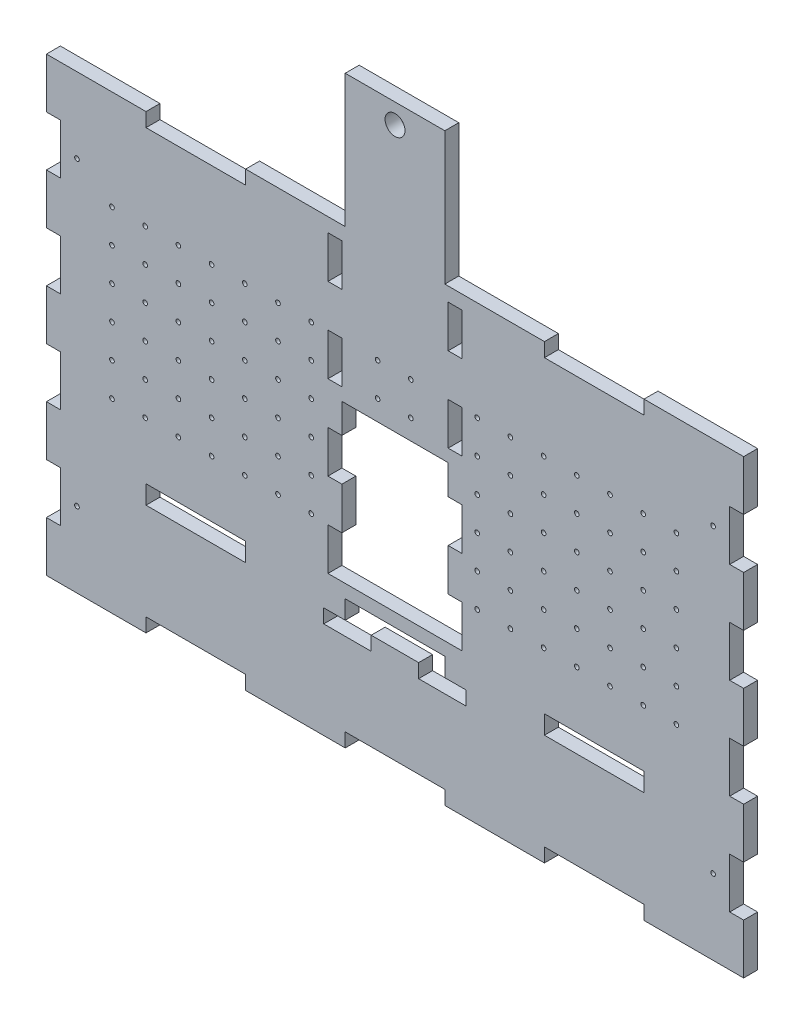
SolidWorks part; units mm, degrees
ref_plane "Front Plane" through (0, 0, 0) normal (0, 0, 1) x (1, 0, 0)
ref_plane "Top Plane" through (0, 0, 0) normal (0, 1, 0) x (1, 0, 0)
ref_plane "Right Plane" through (0, 0, 0) normal (1, 0, 0) x (0, 0, -1)
sketch "Sketch1" plane through (0, 0, 0) normal (0, 0, 1) x (1, 0, 0)
  line L1 (-127.8759, 88.4641) -> (138.8241, 88.4641)
  line L2 (-127.8759, 88.4641) -> (-127.8759, -84.2559)
  line L3 (-127.8759, -84.2559) -> (138.8241, -84.2559)
  line L4 (138.8241, 88.4641) -> (138.8241, -84.2559)
  dimension "D1" = 266.7
  dimension "D2" = 172.72
extrude "Boss-Extrude1" add sketch "Sketch1" along normal blind 5.334
sketch "Sketch2" plane through (0, 0, 5.334) normal (0, 0, 1) x (1, 0, 0)
  line L0 (-127.8759, -84.2559) -> (138.8241, -84.2559) construction
  line L1 (-89.7759, -84.2559) -> (-51.6759, -84.2559)
  line L2 (-89.7759, -84.2559) -> (-89.7759, -78.9219)
  line L3 (-89.7759, -78.9219) -> (-51.6759, -78.9219)
  line L4 (-51.6759, -84.2559) -> (-51.6759, -78.9219)
  line L5 (-89.7759, -78.9219) -> (-127.8759, -78.9219) construction
  line L6 (-13.5759, -84.2559) -> (24.5241, -84.2559)
  line L7 (-13.5759, -84.2559) -> (-13.5759, -78.9219)
  line L8 (-13.5759, -78.9219) -> (24.5241, -78.9219)
  line L9 (24.5241, -84.2559) -> (24.5241, -78.9219)
  line L10 (62.6241, -84.2559) -> (100.7241, -84.2559)
  line L11 (62.6241, -84.2559) -> (62.6241, -78.9219)
  line L12 (62.6241, -78.9219) -> (100.7241, -78.9219)
  line L13 (100.7241, -84.2559) -> (100.7241, -78.9219)
  line L14 (-127.8759, 88.4641) -> (-127.8759, -84.2559) construction
  line L15 (-51.6759, -78.9219) -> (-13.5759, -78.9219) construction
  line L16 (24.5241, -78.9219) -> (62.6241, -78.9219) construction
  line L17 (62.6241, -78.9219) -> (62.364, -79.7896) construction
  line L18 (100.7241, -78.9219) -> (138.8241, -78.9219) construction
  line L19 (138.8241, -84.2559) -> (138.8241, 88.4641) construction
  line L20 (-127.8759, 2.1041) -> (138.8241, 2.1041) construction
  line L21 (100.7241, 88.4641) -> (100.7241, 83.1301)
  line L22 (62.6241, 83.1301) -> (100.7241, 83.1301)
  line L23 (62.6241, 88.4641) -> (62.6241, 83.1301)
  line L24 (24.5241, 88.4641) -> (24.5241, 83.1301)
  line L25 (-13.5759, 83.1301) -> (24.5241, 83.1301)
  line L26 (-13.5759, 88.4641) -> (-13.5759, 83.1301)
  line L27 (-51.6759, 88.4641) -> (-51.6759, 83.1301)
  line L28 (-89.7759, 83.1301) -> (-51.6759, 83.1301)
  line L29 (-89.7759, 88.4641) -> (-89.7759, 83.1301)
  line L30 (62.6241, 88.4641) -> (100.7241, 88.4641)
  line L31 (-13.5759, 88.4641) -> (24.5241, 88.4641)
  line L32 (-89.7759, 88.4641) -> (-51.6759, 88.4641)
  dimension "D1" = 5.334
extrude "Cut-Extrude1" cut sketch "Sketch2" against normal through all
sketch "Sketch5" plane through (0, 0, 5.334) normal (0, 0, 1) x (1, 0, 0)
  line L0 (-51.6759, -34.8224) -> (-13.5759, -34.8224) construction
  line L1 (-89.7759, -34.8224) -> (-51.6759, -34.8224)
  line L2 (-89.7759, -34.8224) -> (-89.7759, -41.9344)
  line L3 (-89.7759, -41.9344) -> (-51.6759, -41.9344)
  line L4 (-51.6759, -34.8224) -> (-51.6759, -41.9344)
  line L5 (-13.5759, -34.8224) -> (24.5241, -34.8224)
  line L6 (-13.5759, -34.8224) -> (-13.5759, -41.9344)
  line L7 (-13.5759, -41.9344) -> (24.5241, -41.9344)
  line L8 (24.5241, -34.8224) -> (24.5241, -41.9344)
  line L9 (62.6241, -34.8224) -> (100.7241, -34.8224)
  line L10 (62.6241, -34.8224) -> (62.6241, -41.9344)
  line L11 (62.6241, -41.9344) -> (100.7241, -41.9344)
  line L12 (100.7241, -34.8224) -> (100.7241, -41.9344)
  line L13 (-51.6759, -41.9344) -> (-13.5759, -41.9344) construction
  line L14 (24.5241, -34.8224) -> (62.6241, -34.8224) construction
  line L15 (24.5241, -41.9344) -> (62.6241, -41.9344) construction
  line L16 (-89.7759, -34.8224) -> (-127.8759, -34.8224) construction
  line L17 (-127.8759, 88.4641) -> (-127.8759, -84.2559) construction
  line L18 (-89.7759, -41.9344) -> (-127.8759, -41.9344) construction
  line L19 (100.7241, -34.8224) -> (138.8241, -34.8224) construction
  line L20 (138.8241, -84.2559) -> (138.8241, 88.4641) construction
  line L21 (100.7241, -41.9344) -> (138.8241, -41.9344) construction
  dimension "D1" = 7.112
extrude "Cut-Extrude3" cut sketch "Sketch5" against normal through all
sketch "Sketch8" plane through (0, 0, 5.334) normal (0, 0, 1) x (1, 0, 0)
  line L0 (-13.5759, -41.9344) -> (24.5241, -41.9344) construction
  line L1 (-21.7977, -47.2684) -> (-3.6478, -47.2684)
  line L2 (-21.7977, -47.2684) -> (-21.7977, -41.9344)
  line L3 (-21.7977, -41.9344) -> (-3.6478, -41.9344)
  line L4 (-3.6478, -47.2684) -> (-3.6478, -41.9344)
  line L5 (-3.6478, -47.2684) -> (14.5022, -47.2684) construction
  line L6 (14.5022, -41.9344) -> (32.6521, -41.9344)
  line L7 (14.5022, -41.9344) -> (14.5022, -47.2684)
  line L8 (14.5022, -47.2684) -> (32.6521, -47.2684)
  line L9 (32.6521, -41.9344) -> (32.6521, -47.2684)
  line L10 (14.5022, -47.2684) -> (14.3218, -49.4005) construction
  line L11 (14.5022, -41.9344) -> (-3.6478, -41.9344) construction
  line L12 (62.6241, -34.8224) -> (62.6241, -41.9344) construction
  line L13 (-51.6759, -41.9344) -> (-51.6759, -34.8224) construction
  dimension "D1" = 5.334
  dimension "D2" = 29.972
  dimension "D3" = 29.8782
extrude "Cut-Extrude6" cut sketch "Sketch8" against normal through all
sketch "Sketch9" plane through (0, 0, 5.334) normal (0, 0, 1) x (1, 0, 0)
  line L0 (-127.8759, 88.4641) -> (-127.8759, -84.2559) construction
  line L1 (-127.8759, -65.0647) -> (-122.5419, -65.0647)
  line L2 (-127.8759, -65.0647) -> (-127.8759, -45.8736)
  line L3 (-127.8759, -45.8736) -> (-122.5419, -45.8736)
  line L4 (-122.5419, -65.0647) -> (-122.5419, -45.8736)
  line L5 (-122.5419, 69.273) -> (-122.5419, 88.4641) construction
  line L6 (-127.8759, -26.6825) -> (-122.5419, -26.6825)
  line L7 (-127.8759, -26.6825) -> (-127.8759, -7.4914)
  line L8 (-127.8759, -7.4914) -> (-122.5419, -7.4914)
  line L9 (-122.5419, -26.6825) -> (-122.5419, -7.4914)
  line L10 (-127.8759, 11.6997) -> (-122.5419, 11.6997)
  line L11 (-127.8759, 11.6997) -> (-127.8759, 30.8908)
  line L12 (-127.8759, 30.8908) -> (-122.5419, 30.8908)
  line L13 (-122.5419, 11.6997) -> (-122.5419, 30.8908)
  line L14 (-127.8759, 50.0819) -> (-122.5419, 50.0819)
  line L15 (-127.8759, 50.0819) -> (-127.8759, 69.273)
  line L16 (-127.8759, 69.273) -> (-122.5419, 69.273)
  line L17 (-122.5419, 50.0819) -> (-122.5419, 69.273)
  line L18 (-89.7759, 88.4641) -> (-127.8759, 88.4641) construction
  line L19 (-122.5419, 50.0819) -> (-122.5419, 30.8908) construction
  line L20 (-122.5419, 11.6997) -> (-122.5419, -7.4914) construction
  line L21 (-122.5419, -26.6825) -> (-122.5419, -45.8736) construction
  line L22 (-122.5419, -65.0647) -> (-122.5419, -84.2559) construction
  line L23 (-127.8759, -84.2559) -> (-89.7759, -84.2559) construction
  line L24 (5.4741, 83.1301) -> (5.4741, -78.9219) construction
  line L25 (-13.5759, 83.1301) -> (24.5241, 83.1301) construction
  line L26 (24.5241, -78.9219) -> (-13.5759, -78.9219) construction
  line L27 (133.4901, -65.0647) -> (133.4901, -84.2559) construction
  line L28 (133.4901, -26.6825) -> (133.4901, -45.8736) construction
  line L29 (133.4901, 11.6997) -> (133.4901, -7.4914) construction
  line L30 (133.4901, 50.0819) -> (133.4901, 30.8908) construction
  line L31 (133.4901, 69.273) -> (133.4901, 88.4641) construction
  line L32 (133.4901, 50.0819) -> (133.4901, 69.273)
  line L33 (138.8241, 69.273) -> (133.4901, 69.273)
  line L34 (138.8241, 50.0819) -> (138.8241, 69.273)
  line L35 (138.8241, 50.0819) -> (133.4901, 50.0819)
  line L36 (133.4901, 11.6997) -> (133.4901, 30.8908)
  line L37 (138.8241, 30.8908) -> (133.4901, 30.8908)
  line L38 (138.8241, 11.6997) -> (138.8241, 30.8908)
  line L39 (138.8241, 11.6997) -> (133.4901, 11.6997)
  line L40 (133.4901, -26.6825) -> (133.4901, -7.4914)
  line L41 (138.8241, -7.4914) -> (133.4901, -7.4914)
  line L42 (138.8241, -26.6825) -> (138.8241, -7.4914)
  line L43 (138.8241, -26.6825) -> (133.4901, -26.6825)
  line L44 (133.4901, -65.0647) -> (133.4901, -45.8736)
  line L45 (138.8241, -45.8736) -> (133.4901, -45.8736)
  line L46 (138.8241, -65.0647) -> (138.8241, -45.8736)
  line L47 (138.8241, -65.0647) -> (133.4901, -65.0647)
  dimension "D1" = 5.334
extrude "Cut-Extrude7" cut sketch "Sketch9" against normal through all
sketch "Sketch10" plane through (0, 88.4641, 0) normal (0, 1, 0) x (1, 0, 0)
  line L1 (24.5241, -5.334) -> (62.6241, -5.334)
  line L2 (24.5241, -5.334) -> (24.5241, 0)
  line L3 (24.5241, 0) -> (62.6241, 0)
  line L4 (62.6241, -5.334) -> (62.6241, 0)
extrude "Boss-Extrude2" add sketch "Sketch10" along normal blind 50.8
sketch "Sketch11" plane through (0, 0, 0) normal (0, 0, -1) x (-1, 0, 0)
  line L0 (-24.5241, 83.1301) -> (-24.5241, 139.2641) construction
  line L1 (-24.5241, 88.4641) -> (-31.1281, 88.4641)
  line L2 (-24.5241, 88.4641) -> (-24.5241, 129.1041)
  line L3 (-24.5241, 129.1041) -> (-31.1281, 129.1041)
  line L4 (-31.1281, 88.4641) -> (-31.1281, 129.1041)
  line L5 (13.5759, 88.4641) -> (51.6759, 88.4641) construction
  dimension "D1" = 6.604
  dimension "D2" = 40.64
  dimension "D3" = 0
extrude "Cut-Extrude8" cut sketch "Sketch11" against normal through all
sketch "Sketch12" plane through (0, 0, 5.334) normal (0, 0, 1) x (1, 0, 0)
  line L0 (62.6241, 139.2641) -> (62.6241, 83.1301) construction
  circle A0 centre (43.5741, 130.4765) radius 3.81
  dimension "D1" = 19.05
extrude "Cut-Extrude9" cut sketch "Sketch12" against normal through all
sketch "Sketch14" plane through (0, 0, 5.334) normal (0, 0, 1) x (1, 0, 0)
  line L0 (-89.7759, 88.4641) -> (-127.8759, 88.4641) construction
  circle A0 centre (-102.7976, 50.3641) radius 0.889
  circle A1 centre (-90.0976, 50.3641) radius 0.889
  circle A2 centre (-77.3976, 50.3641) radius 0.889
  circle A3 centre (-64.6976, 50.3641) radius 0.889
  circle A4 centre (-51.9976, 50.3641) radius 0.889
  circle A5 centre (-39.2976, 50.3641) radius 0.889
  circle A6 centre (-26.5976, 50.3641) radius 0.889
  circle A8 centre (-1.1976, 50.3641) radius 0.889
  circle A9 centre (11.5024, 50.3641) radius 0.889
  circle A11 centre (36.9024, 50.3641) radius 0.889
  circle A12 centre (49.6024, 50.3641) radius 0.889
  circle A13 centre (62.3024, 50.3641) radius 0.889
  circle A14 centre (75.0024, 50.3641) radius 0.889
  circle A15 centre (87.7024, 50.3641) radius 0.889
  circle A16 centre (100.4024, 50.3641) radius 0.889
  circle A17 centre (113.1024, 50.3641) radius 0.889
  circle A18 centre (-102.7976, 37.6641) radius 0.889
  circle A19 centre (-90.0976, 37.6641) radius 0.889
  circle A20 centre (-77.3976, 37.6641) radius 0.889
  circle A21 centre (-64.6976, 37.6641) radius 0.889
  circle A22 centre (-51.9976, 37.6641) radius 0.889
  circle A23 centre (-39.2976, 37.6641) radius 0.889
  circle A24 centre (-26.5976, 37.6641) radius 0.889
  circle A26 centre (-1.1976, 37.6641) radius 0.889
  circle A27 centre (11.5024, 37.6641) radius 0.889
  circle A29 centre (36.9024, 37.6641) radius 0.889
  circle A30 centre (49.6024, 37.6641) radius 0.889
  circle A31 centre (62.3024, 37.6641) radius 0.889
  circle A32 centre (75.0024, 37.6641) radius 0.889
  circle A33 centre (87.7024, 37.6641) radius 0.889
  circle A34 centre (100.4024, 37.6641) radius 0.889
  circle A35 centre (113.1024, 37.6641) radius 0.889
  circle A36 centre (-102.7976, 24.9641) radius 0.889
  circle A37 centre (-90.0976, 24.9641) radius 0.889
  circle A38 centre (-77.3976, 24.9641) radius 0.889
  circle A39 centre (-64.6976, 24.9641) radius 0.889
  circle A40 centre (-51.9976, 24.9641) radius 0.889
  circle A41 centre (-39.2976, 24.9641) radius 0.889
  circle A42 centre (-26.5976, 24.9641) radius 0.889
  circle A44 centre (-1.1976, 24.9641) radius 0.889
  circle A45 centre (11.5024, 24.9641) radius 0.889
  circle A47 centre (36.9024, 24.9641) radius 0.889
  circle A48 centre (49.6024, 24.9641) radius 0.889
  circle A49 centre (62.3024, 24.9641) radius 0.889
  circle A50 centre (75.0024, 24.9641) radius 0.889
  circle A51 centre (87.7024, 24.9641) radius 0.889
  circle A52 centre (100.4024, 24.9641) radius 0.889
  circle A53 centre (113.1024, 24.9641) radius 0.889
  circle A54 centre (-102.7976, 12.2641) radius 0.889
  circle A55 centre (-90.0976, 12.2641) radius 0.889
  circle A56 centre (-77.3976, 12.2641) radius 0.889
  circle A57 centre (-64.6976, 12.2641) radius 0.889
  circle A58 centre (-51.9976, 12.2641) radius 0.889
  circle A59 centre (-39.2976, 12.2641) radius 0.889
  circle A60 centre (-26.5976, 12.2641) radius 0.889
  circle A65 centre (36.9024, 12.2641) radius 0.889
  circle A66 centre (49.6024, 12.2641) radius 0.889
  circle A67 centre (62.3024, 12.2641) radius 0.889
  circle A68 centre (75.0024, 12.2641) radius 0.889
  circle A69 centre (87.7024, 12.2641) radius 0.889
  circle A70 centre (100.4024, 12.2641) radius 0.889
  circle A71 centre (113.1024, 12.2641) radius 0.889
  circle A72 centre (-102.7976, -0.4359) radius 0.889
  circle A73 centre (-90.0976, -0.4359) radius 0.889
  circle A74 centre (-77.3976, -0.4359) radius 0.889
  circle A75 centre (-64.6976, -0.4359) radius 0.889
  circle A76 centre (-51.9976, -0.4359) radius 0.889
  circle A77 centre (-39.2976, -0.4359) radius 0.889
  circle A78 centre (-26.5976, -0.4359) radius 0.889
  circle A79 centre (-13.8976, -0.4359) radius 0.889
  circle A80 centre (-1.1976, -0.4359) radius 0.889
  circle A81 centre (11.5024, -0.4359) radius 0.889
  circle A82 centre (24.2024, -0.4359) radius 0.889
  circle A83 centre (36.9024, -0.4359) radius 0.889
  circle A84 centre (49.6024, -0.4359) radius 0.889
  circle A85 centre (62.3024, -0.4359) radius 0.889
  circle A86 centre (75.0024, -0.4359) radius 0.889
  circle A87 centre (87.7024, -0.4359) radius 0.889
  circle A88 centre (100.4024, -0.4359) radius 0.889
  circle A89 centre (113.1024, -0.4359) radius 0.889
  circle A90 centre (-102.7976, -13.1359) radius 0.889
  circle A91 centre (-90.0976, -13.1359) radius 0.889
  circle A92 centre (-77.3976, -13.1359) radius 0.889
  circle A93 centre (-64.6976, -13.1359) radius 0.889
  circle A94 centre (-51.9976, -13.1359) radius 0.889
  circle A95 centre (-39.2976, -13.1359) radius 0.889
  circle A96 centre (-26.5976, -13.1359) radius 0.889
  circle A97 centre (-13.8976, -13.1359) radius 0.889
  circle A98 centre (-1.1976, -13.1359) radius 0.889
  circle A99 centre (11.5024, -13.1359) radius 0.889
  circle A100 centre (24.2024, -13.1359) radius 0.889
  circle A101 centre (36.9024, -13.1359) radius 0.889
  circle A102 centre (49.6024, -13.1359) radius 0.889
  circle A103 centre (62.3024, -13.1359) radius 0.889
  circle A104 centre (75.0024, -13.1359) radius 0.889
  circle A105 centre (87.7024, -13.1359) radius 0.889
  circle A106 centre (100.4024, -13.1359) radius 0.889
  circle A107 centre (113.1024, -13.1359) radius 0.889
  circle A108 centre (-1.1976, 12.2641) radius 0.889 [skipped]
  circle A110 centre (11.5024, 12.2641) radius 0.889 [skipped]
  circle A116 centre (24.2024, 50.3641) radius 0.889 [skipped]
  circle A117 centre (-13.8976, 50.3641) radius 0.889 [skipped]
  dimension "D1" = 18
  dimension "D2" = 38.1
  dimension "D4" = 1.778
  dimension "D3" = 6
extrude "Cut-Extrude11" cut sketch "Sketch14" against normal through all
sketch "Sketch15" plane through (0, 0, 5.334) normal (0, 0, 1) x (1, 0, 0)
  line L1 (31.1281, 129.1041) -> (24.5241, 129.1041)
  line L2 (31.1281, 129.1041) -> (31.1281, 139.2641)
  line L3 (31.1281, 139.2641) -> (24.5241, 139.2641)
  line L4 (24.5241, 129.1041) -> (24.5241, 139.2641)
extrude "Cut-Extrude12" cut sketch "Sketch15" against normal through all
sketch "Sketch16" plane through (0, 0, 5.334) normal (0, 0, 1) x (1, 0, 0)
  line L0 (5.4741, 83.1301) -> (5.4741, -78.9219) construction
  line L1 (-14.8459, 29.9476) -> (25.7941, 29.9476)
  line L2 (-14.8459, 29.9476) -> (-14.8459, -29.7424)
  line L3 (-14.8459, -29.7424) -> (25.7941, -29.7424)
  line L4 (25.7941, 29.9476) -> (25.7941, -29.7424)
  line L5 (-13.5759, 83.1301) -> (24.5241, 83.1301) construction
  line L6 (24.5241, -78.9219) -> (-13.5759, -78.9219) construction
  line L7 (24.5241, -34.8224) -> (-13.5759, -34.8224) construction
  dimension "D1" = 59.69
  dimension "D2" = 40.64
  dimension "D3" = 20.32
  dimension "D4" = 5.08
extrude "Cut-Extrude13" cut sketch "Sketch16" against normal through all
sketch "Sketch17" plane through (0, 0, 5.334) normal (0, 0, 1) x (1, 0, 0)
  line L0 (-14.8459, 29.9476) -> (-14.8459, -29.7424) construction
  line L1 (-14.8459, -29.7424) -> (-20.1799, -29.7424)
  line L2 (-14.8459, -29.7424) -> (-14.8459, -13.6178)
  line L3 (-14.8459, -13.6178) -> (-20.1799, -13.6178)
  line L4 (-20.1799, -29.7424) -> (-20.1799, -13.6178)
  line L5 (-14.8459, 2.5069) -> (-20.1799, 2.5069)
  line L6 (-14.8459, 2.5069) -> (-14.8459, 18.6315)
  line L7 (-14.8459, 18.6315) -> (-20.1799, 18.6315)
  line L8 (-20.1799, 2.5069) -> (-20.1799, 18.6315)
  line L9 (-20.1799, -13.6178) -> (-20.1799, 2.5069) construction
  line L10 (-20.1799, 50.8808) -> (-14.8459, 50.8808)
  line L11 (-20.1799, 50.8808) -> (-20.1799, 34.7562)
  line L12 (-20.1799, 34.7562) -> (-14.8459, 34.7562)
  line L13 (-14.8459, 50.8808) -> (-14.8459, 34.7562)
  line L14 (-20.1799, 67.0055) -> (-14.8459, 67.0055)
  line L15 (-20.1799, 67.0055) -> (-20.1799, 83.1301)
  line L16 (-20.1799, 83.1301) -> (-14.8459, 83.1301)
  line L17 (-14.8459, 67.0055) -> (-14.8459, 83.1301)
  line L18 (-20.1799, 18.6315) -> (-20.1799, 34.7562) construction
  line L19 (-20.1799, 67.0055) -> (-20.1799, 50.8808) construction
  line L20 (5.4741, 83.1301) -> (5.4741, -78.9219) construction
  line L21 (-13.5759, 83.1301) -> (24.5241, 83.1301) construction
  line L22 (24.5241, -78.9219) -> (-13.5759, -78.9219) construction
  line L23 (31.1281, 67.0055) -> (31.1281, 50.8808) construction
  line L24 (31.1281, 18.6315) -> (31.1281, 34.7562) construction
  line L25 (31.1281, -13.6178) -> (31.1281, 2.5069) construction
  line L26 (25.7941, 67.0055) -> (25.7941, 83.1301)
  line L27 (31.1281, 83.1301) -> (25.7941, 83.1301)
  line L28 (31.1281, 67.0055) -> (31.1281, 83.1301)
  line L29 (31.1281, 67.0055) -> (25.7941, 67.0055)
  line L30 (25.7941, 50.8808) -> (25.7941, 34.7562)
  line L31 (31.1281, 34.7562) -> (25.7941, 34.7562)
  line L32 (31.1281, 50.8808) -> (31.1281, 34.7562)
  line L33 (31.1281, 50.8808) -> (25.7941, 50.8808)
  line L34 (31.1281, 2.5069) -> (31.1281, 18.6315)
  line L35 (25.7941, 18.6315) -> (31.1281, 18.6315)
  line L36 (25.7941, 2.5069) -> (25.7941, 18.6315)
  line L37 (25.7941, 2.5069) -> (31.1281, 2.5069)
  line L38 (31.1281, -29.7424) -> (31.1281, -13.6178)
  line L39 (25.7941, -13.6178) -> (31.1281, -13.6178)
  line L40 (25.7941, -29.7424) -> (25.7941, -13.6178)
  line L41 (25.7941, -29.7424) -> (31.1281, -29.7424)
  dimension "D1" = 0
  dimension "D2" = 5.334
  dimension "D3" = 5.334
  dimension "D4" = 5.334
extrude "Cut-Extrude14" cut sketch "Sketch17" against normal through all
sketch "Sketch18" plane through (0, 0, 5.334) normal (0, 0, 1) x (1, 0, 0)
  line L0 (24.5241, 83.1301) -> (24.5241, 148.9274) construction
  line L1 (31.1281, 139.2641) -> (62.6241, 139.2641) construction
  line L2 (-13.5759, 83.1301) -> (24.5241, 83.1301)
  line L3 (-13.5759, 83.1301) -> (-13.5759, 139.2641)
  line L4 (-13.5759, 139.2641) -> (24.5241, 139.2641)
  line L5 (24.5241, 83.1301) -> (24.5241, 139.2641)
  dimension "D1" = 0
extrude "Boss-Extrude3" add sketch "Sketch18" against normal blind 5.334
sketch "Sketch19" plane through (0, 0, 5.334) normal (0, 0, 1) x (1, 0, 0)
  line L1 (31.1281, 88.4641) -> (65.8849, 88.4641)
  line L2 (31.1281, 88.4641) -> (31.1281, 143.4078)
  line L3 (31.1281, 143.4078) -> (65.8849, 143.4078)
  line L4 (65.8849, 88.4641) -> (65.8849, 143.4078)
extrude "Cut-Extrude15" cut sketch "Sketch19" against normal through all
sketch "Sketch20" plane through (0, 0, 5.334) normal (0, 0, 1) x (1, 0, 0)
  line L0 (5.4741, 139.2641) -> (5.4741, 29.9476) construction
  line L1 (24.5241, 139.2641) -> (-13.5759, 139.2641) construction
  line L2 (25.7941, 29.9476) -> (-14.8459, 29.9476) construction
  circle A0 centre (5.4741, 131.6441) radius 3.81
  dimension "D1" = 7.62
  dimension "D3" = 7.62
  dimension "D2" = 0
extrude "Cut-Extrude16" cut sketch "Sketch20" against normal through all contours A0
sketch "Sketch21" plane through (0, 0, 5.334) normal (0, 0, 1) x (1, 0, 0)
  line L0 (133.4901, 59.6775) -> (-122.5419, 59.6775) construction
  line L1 (133.4901, 69.273) -> (133.4901, 50.0819) construction
  line L2 (-122.5419, 50.0819) -> (-122.5419, 69.273) construction
  line L3 (-122.5419, -55.4692) -> (133.4901, -55.4692) construction
  line L4 (-122.5419, -65.0647) -> (-122.5419, -45.8736) construction
  line L5 (133.4901, -45.8736) -> (133.4901, -65.0647) construction
  line L6 (138.8241, 2.1041) -> (-127.8759, 2.1041) construction
  line L7 (138.8241, -7.4914) -> (138.8241, 11.6997) construction
  line L8 (-127.8759, 11.6997) -> (-127.8759, -7.4914) construction
  line L9 (5.4741, 139.2641) -> (5.4741, -78.9219) construction
  line L10 (24.5241, 139.2641) -> (-13.5759, 139.2641) construction
  line L11 (24.5241, -78.9219) -> (-13.5759, -78.9219) construction
  circle A0 centre (127.1401, 59.6775) radius 0.889
  circle A1 centre (-116.1919, 59.6775) radius 0.889
  circle A2 centre (-116.1919, -55.4692) radius 0.889
  circle A3 centre (127.1401, -55.4692) radius 0.889
  dimension "D1" = 1.778
  dimension "D2" = 0
  dimension "D3" = 6.35
extrude "Cut-Extrude17" cut sketch "Sketch21" against normal through all
equation "\"MDF\"= .21in"
equation "\"Foamcore\"= .13in"
equation "\"Gmaterial\"= \"MDF\""
equation "\"D1@Boss-Extrude1\"=\"MDF\""
equation "\"D1@Sketch2\"=\"MDF\""
equation "\"D1@Sketch5\"=\"MDF\"+0.07"
equation "\"D1@Sketch8\"=\"MDF\""
equation "\"D1@Sketch9\"=\"MDF\""
equation "\"D1@Sketch11\"=\"MDF\"+.05"
equation "\"D2@Sketch17\"=\"MDF\""
equation "\"D3@Sketch17\"=\"MDF\""
equation "\"D4@Sketch17\"=\"MDF\""
equation "\"D1@Boss-Extrude3\"=\"MDF\""
